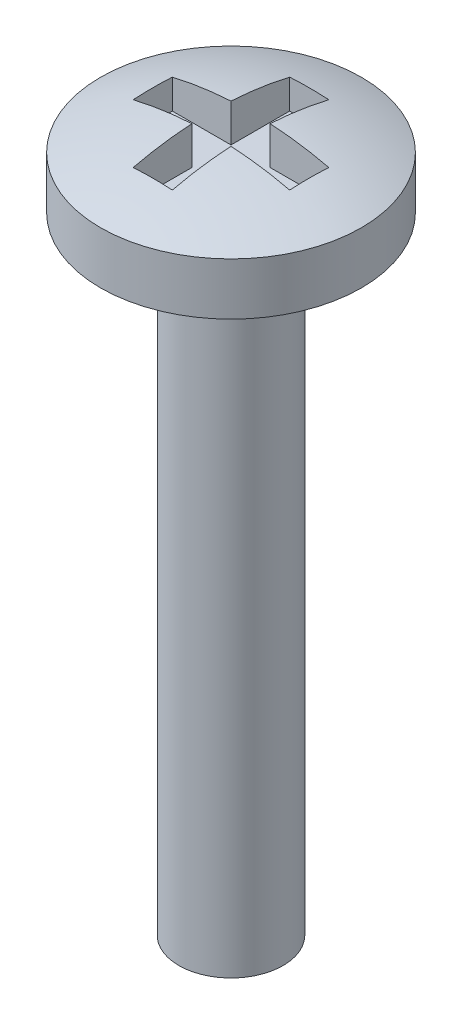
SolidWorks part; units mm, degrees
material "1023 Carbon Steel Sheet (SS)"
ref_plane "Front Plane" through (0, 0, 0) normal (0, 0, 1) x (1, 0, 0)
ref_plane "Top Plane" through (0, 0, 0) normal (0, 1, 0) x (1, 0, 0)
ref_plane "Right Plane" through (0, 0, 0) normal (1, 0, 0) x (0, 0, -1)
ref_plane "Top Plane1" through (0, 13.5, 0) normal (0, 1, 0) x (1, 0, 0)
sketch "Sketch1" plane through (0, 0, 0) normal (0, 1, 0) x (1, 0, 0)
  circle A0 centre (0, 0) radius 1
  dimension "D1" = 2
extrude "Boss-Extrude1" add sketch "Sketch1" along normal blind 12
sketch "Sketch2" plane through (0, 12, 0) normal (0, 1, 0) x (1, 0, 0)
  circle A0 centre (0, 0) radius 2.5
  dimension "D1" = 5
extrude "Boss-Extrude2" add sketch "Sketch2" along normal blind 1
dome "Dome1" faces to dome 1 distance 0.5 reverse direction no elliptical dome no face at (0, 13, 2.5) parameters "D1"=0.5
sketch "Sketch3" plane through (0, 13.5, 0) normal (0, 1, 0) x (1, 0, 0)
  line L0 (-2.5, 0) -> (2.5, 0) construction
  line L1 (0, 2.5) -> (0, -2.5) construction
  line L2 (-1.5, 0.375) -> (1.5, -0.375) construction
  line L3 (-1.5, 0.375) -> (1.5, 0.375)
  line L4 (-1.5, 0.375) -> (-1.5, -0.375)
  line L5 (-1.5, -0.375) -> (1.5, -0.375)
  line L6 (1.5, 0.375) -> (1.5, -0.375)
  line L7 (0.375, 1.5) -> (-0.375, -1.5) construction
  line L8 (-0.375, 1.5) -> (0.375, 1.5)
  line L9 (-0.375, 1.5) -> (-0.375, -1.5)
  line L10 (-0.375, -1.5) -> (0.375, -1.5)
  line L11 (0.375, 1.5) -> (0.375, -1.5)
  circle A0 centre (0, 0) radius 2.5 construction
  dimension "D1" = 1.5
  dimension "D2" = 1.5
  dimension "D3" = 0.75
  dimension "D4" = 0.75
extrude "Cut-Extrude1" cut sketch "Sketch3" against normal blind 0.75 contours L9 L3 L4 L5 | L11 L3 L9 L5 | L11 L8 L9 L3 | L3 L11 L5 L6 | L11 L5 L9 L10 region at (-0.9375, 13.5, 0) region at (0, 13.5, -0.9375) region at (0, 13.5, 0) region at (0.9375, 13.5, 0) region at (0, 13.5, 0.9375)
